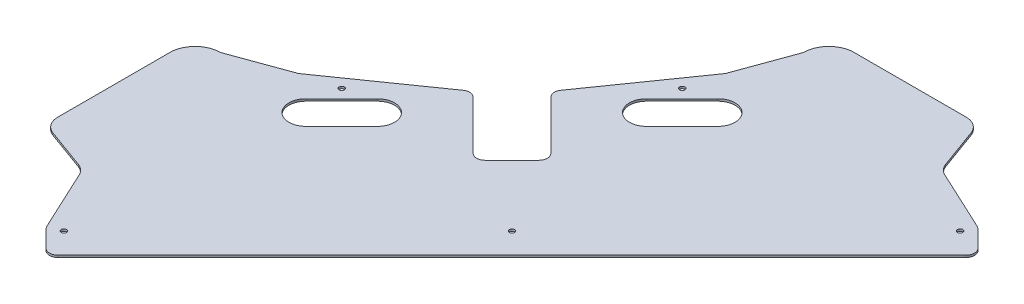
SolidWorks part; units mm, degrees
material "PE High Density"
ref_plane "Front Plane" through (0, 0, 0) normal (0, 0, 1) x (1, 0, 0)
ref_plane "Top Plane" through (0, 0, 0) normal (0, 1, 0) x (1, 0, 0)
ref_plane "Right Plane" through (0, 0, 0) normal (1, 0, 0) x (0, 0, -1)
sketch "Sketch1" plane through (0, 0, 0) normal (0, 1, 0) x (1, 0, 0)
  line L0 (0, 0) -> (597.187, -597.187) construction
  line L1 (246.957, -947.417) -> (947.417, -246.957)
  line L2 (246.957, -947.417) -> (211.036, -911.496)
  line L6 (593.725, 0) -> (0, 0) construction
  line L7 (0, 0) -> (0, -593.725) construction
  line L10 (76.2, -776.9243) -> (76.2, -552.45)
  line L11 (76.2, -552.45) -> (437.7875, -437.7875) construction
  line L12 (552.45, -76.2) -> (437.7875, -437.7875) construction
  line L13 (776.9243, -76.2) -> (552.45, -76.2)
  line L14 (0, -593.725) -> (114.3, -593.725) construction
  line L15 (444.5227, -502.8943) -> (354.7201, -413.0918)
  line L16 (444.5227, -502.8943) -> (473.7085, -473.7085) construction
  line L17 (521.0735, -200.5063) -> (413.0918, -354.7201)
  line L18 (502.8943, -444.5227) -> (413.0918, -354.7201)
  line L19 (419.827, -419.827) -> (0, -839.6539) construction
  line L20 (76.2, -552.45) -> (114.3, -552.45)
  line L24 (444.5227, -502.8943) -> (502.8943, -444.5227)
  line L26 (552.45, -76.2) -> (552.45, -114.3)
  line L27 (114.3, -552.45) -> (200.5063, -521.0735)
  line L28 (200.5063, -521.0735) -> (354.7201, -413.0918)
  line L29 (552.45, -114.3) -> (521.0735, -200.5063)
  line L32 (947.417, -246.957) -> (911.496, -211.036)
  line L33 (211.036, -911.496) -> (163.0194, -808.524)
  line L34 (163.0194, -808.524) -> (76.2, -776.9243)
  line L35 (808.524, -163.0194) -> (776.9243, -76.2)
  line L36 (911.496, -211.036) -> (808.524, -163.0194)
  circle A0 centre (0, 0) radius 593.725 construction
  circle A1 centre (0, 0) radius 542.925 construction
  point P7 (597.187, -597.187)
  point P8 (419.827, -419.827)
  dimension "D14" = 50.8
  dimension "D1" = 250.825
  dimension "D2" = 844.55
  dimension "D3" = 45
  dimension "D4" = 990.6
  dimension "D5" = 241.3
  dimension "D6" = 20
  dimension "D7" = 25.4
  dimension "D8" = 76.2
  dimension "D9" = 41.275
  dimension "D10" = 38.1
  dimension "D11" = 41.275
  dimension "D12" = 76.2
  dimension "D13" = 160
  dimension "D15" = 165
  dimension "D16" = 50.8
  dimension "D17" = 50.8
  dimension "D18" = 70
extrude "Boss-Extrude1" add sketch "Sketch1" along normal blind 3.175 contours L13 L26 L29 L17 L18 L24 L15 L28 L27 L20 L10 L2 L1 L32 region at (481.7607, 0, 481.7607)
ref_plane "Plane1" through (0, 0, 0) normal (-0.7071, 0, 0.7071) x (0.7071, 0, 0.7071)
fillet "Fillet3" radius 38.1 2 edges at (76.2, 1.5875, 552.45) (552.45, 1.5875, 76.2)
sketch "Sketch7" plane through (0, 3.175, 0) normal (0, 1, 0) x (1, 0, 0)
  line L0 (228.9965, -902.5157) -> (902.5157, -228.9965)
  line L1 (246.957, -947.417) -> (947.417, -246.957) construction
  line L2 (0, 0) -> (597.187, -597.187) construction
  line L3 (246.957, -947.417) -> (211.036, -911.496) construction
  line L4 (76.2, -776.9243) -> (76.2, -590.55) construction
  line L5 (114.3, -552.45) -> (200.5063, -521.0735) construction
  line L6 (444.5227, -502.8943) -> (354.7201, -413.0918) construction
  line L7 (200.5063, -521.0735) -> (354.7201, -413.0918) construction
  point P2 (95.25, -579.6562)
  point P3 (252.1974, -508.1347)
  point P5 (508.1347, -252.1974)
  point P11 (565.7561, -565.7561)
  point P23 (579.6562, -95.25)
  dimension "D1" = 44.45
  dimension "D2" = 19.05
  dimension "D3" = 19.05
  dimension "D4" = 19.05
  dimension "D5" = 139.7
  dimension "D6" = 19.05
hole_wizard "5/16 (0.3125) Dowel Hole1" positions "Sketch8" profile "Sketch9" hole size "5/16" standard "ANSI Inch" end condition up to next
sketch "Sketch8" plane through (0, 3.175, 0) normal (0, 1, 0) x (1, 0, 0)
  line L0 (228.9965, -902.5157) -> (902.5157, -228.9965) construction
  point P3 (252.1974, -508.1347)
  point P6 (508.1347, -252.1974)
  point P12 (902.5157, -228.9965)
  point P15 (228.9965, -902.5157)
  point P18 (565.7561, -565.7561)
sketch "Sketch9" plane through (252.1974, 3.175, 508.1347) normal (1, 0, 0) x (0, 0, 1)
  line L0 (0, 0) -> (0, 3.175)
  line L1 (0, 3.175) -> (3.9688, 3.175)
  line L2 (3.9688, 3.175) -> (3.9687, 0)
  line L5 (3.9687, 0) -> (0, 0)
  line L11 (0, -6.35) -> (0, 107.95) construction
  dimension "Thru Hole Dia." = 7.9375
  dimension "Thru Hole Depth" = 3.175
sketch "Sketch11" plane through (0, 3.175, 0) normal (0, 1, 0) x (1, 0, 0)
  line L0 (252.1974, -508.1347) -> (283.6283, -539.5656) construction
  line L1 (310.5691, -512.6248) -> (256.6875, -566.5064) construction
  line L3 (-38.8909, 38.8909) -> (38.8909, -38.8909) construction
  line L4 (512.6248, -310.5691) -> (566.5064, -256.6875) construction
  line L5 (444.5227, -502.8943) -> (354.7201, -413.0918) construction
  point P10 (283.6283, -539.5656)
  point P11 (539.5656, -283.6283)
  dimension "D1" = 44.45
  dimension "3" = 76.2
hole_wizard "1 (2) Dowel Slot1" positions "Sketch12" profile "Sketch13" size "1" standard "ANSI Inch" slot yes end condition up to next
sketch "Sketch12" plane through (0, 3.175, 0) normal (0, 1, 0) x (1, 0, 0)
  line L0 (238.727, -584.4669) -> (328.5296, -494.6643) construction
  line L1 (444.5227, -502.8943) -> (354.7201, -413.0918) construction
  point P0 (283.6283, -539.5656)
  point P5 (539.5656, -283.6283)
  dimension "D1" = 127
sketch "Sketch13" plane through (283.6283, 3.175, 539.5656) normal (1, 0, 0) x (0, 0, 1)
  line L0 (0, 0) -> (0, 3.175)
  line L1 (0, 3.175) -> (25.4, 3.175)
  line L2 (25.4, 3.175) -> (25.4, 0)
  line L5 (25.4, 0) -> (0, 0)
  line L11 (0, -6.35) -> (0, 107.95) construction
  dimension "Thru Hole Dia." = 50.8
  dimension "Thru Hole Depth" = 3.175
fillet "Fillet4" radius 25.4 6 edges at (211.036, 1.5875, 911.496) (776.9243, 1.5875, 76.2) (808.524, 1.5875, 163.0194) (911.496, 1.5875, 211.036) (76.2, 1.5875, 776.9243) (163.0194, 1.5875, 808.524)
fillet "Fillet6" radius 12.7 10 edges at (413.0918, 1.5875, 354.7201) (502.8943, 1.5875, 444.5227) (444.5227, 1.5875, 502.8943) (354.7201, 1.5875, 413.0918) (114.3, 1.5875, 552.45) (200.5063, 1.5875, 521.0735) (521.0735, 1.5875, 200.5063) (552.45, 1.5875, 114.3) (947.417, 1.5875, 246.957) (246.957, 1.5875, 947.417)
